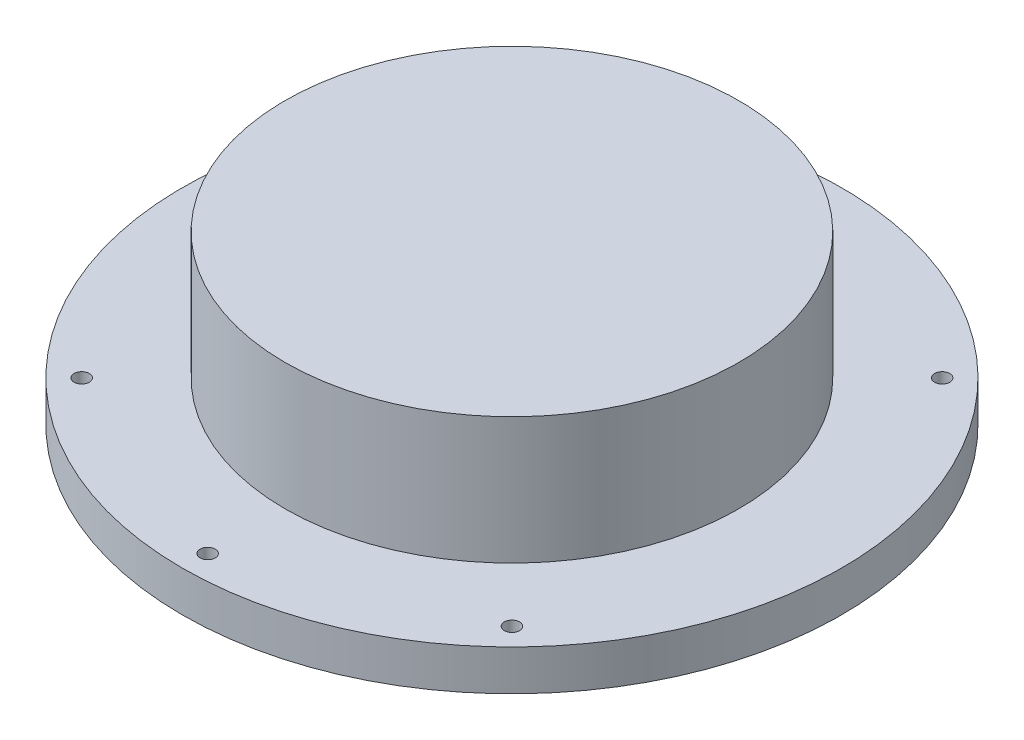
SolidWorks part; units mm, degrees
ref_plane "Front Plane" through (0, 0, 0) normal (0, 0, 1) x (1, 0, 0)
ref_plane "Top Plane" through (0, 0, 0) normal (0, 1, 0) x (1, 0, 0)
ref_plane "Right Plane" through (0, 0, 0) normal (1, 0, 0) x (0, 0, -1)
sketch "Sketch1" plane through (0, 0, 0) normal (0, 1, 0) x (1, 0, 0)
  line L0 (0, 0) -> (0, -65) construction
  circle A0 centre (0, 0) radius 65
  circle A1 centre (0, -60) radius 1.5
  circle A2 centre (-42.4264, -42.4264) radius 1.5
  circle A3 centre (-60, 0) radius 1.5 construction
  circle A4 centre (-42.4264, 42.4264) radius 1.5
  circle A5 centre (0, 60) radius 1.5
  circle A6 centre (42.4264, 42.4264) radius 1.5
  circle A7 centre (60, 0) radius 1.5 construction
  circle A8 centre (42.4264, -42.4264) radius 1.5
  point P22 (0, 0)
  dimension "D2" = 3
  dimension "D3" = 130
  dimension "D4" = 5
  dimension "D1" = 8
extrude "Boss-Extrude1" add sketch "Sketch1" along normal blind 8
sketch "Sketch3" plane through (0, 8, 0) normal (0, 1, 0) x (1, 0, 0)
  circle A0 centre (0, 0) radius 44.746
extrude "Boss-Extrude2" add sketch "Sketch3" along normal blind 25
sketch "Sketch2" plane through (0, 0, 0) normal (1, 0, 0) x (0, 0, -1)
  line L0 (0, 0) -> (0, 175.4685) construction
  line L1 (-36, 8) -> (-36, 44.2388)
  line L6 (65, 8) -> (-65, 8) construction
  line L7 (36, 8) -> (36, 69.0304)
  line L8 (-36, 8) -> (36, 8)
  arc A0 (36, 69.0304) -> (-36, 44.2388) centre (-7, 76.964) ccw
  circle A1 centre (-7, 76.964) radius 4
  point P5 (0, 8)
  point P12 (38.3979, 69.3946)
  point P13 (31.1133, 69.0304)
  dimension "D2" = 8
  dimension "D1" = 7
  dimension "D3" = 72
